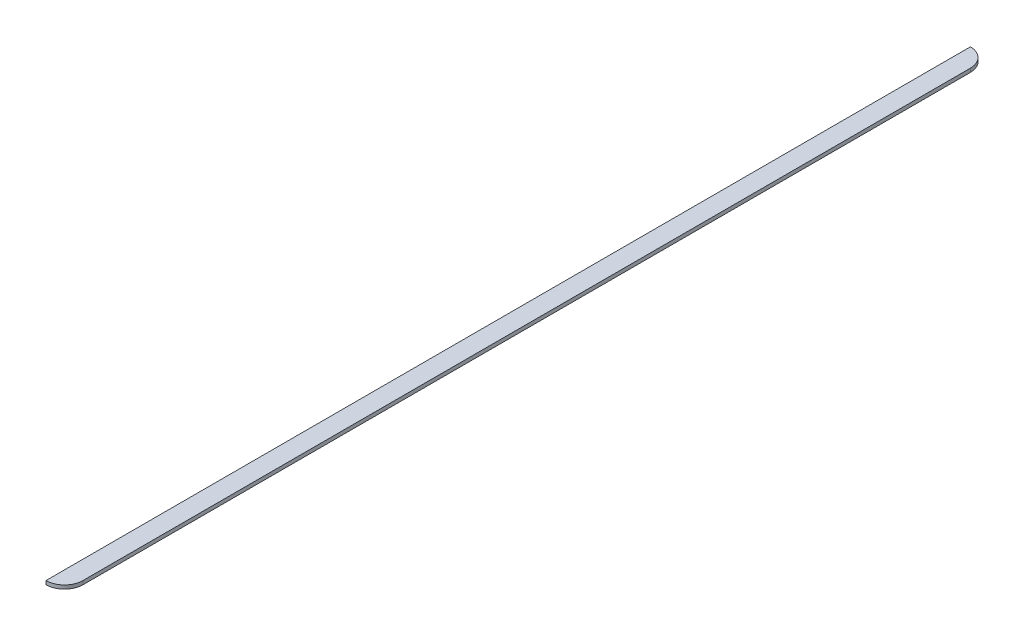
SolidWorks part; units mm, degrees
ref_plane "前视基准面" through (0, 0, 0) normal (0, 0, 1) x (1, 0, 0)
ref_plane "上视基准面" through (0, 0, 0) normal (0, 1, 0) x (1, 0, 0)
ref_plane "右视基准面" through (0, 0, 0) normal (1, 0, 0) x (0, 0, -1)
sketch "草图1" plane through (0, 0, 0) normal (0, 0, 1) x (1, 0, 0)
  line L1 (0, 0) -> (10, 0)
  line L2 (0, 0) -> (0, 2)
  line L3 (0, 2) -> (10, 2)
  line L4 (10, 0) -> (10, 2)
  dimension "D1" = 10
  dimension "D2" = 2
extrude "凸台-拉伸1" add sketch "草图1" along normal mid plane 500 contours L3 L4 L1 L2
fillet "圆角1" radius 10 2 edges at (10, 1, -250) (10, 1, 250)
